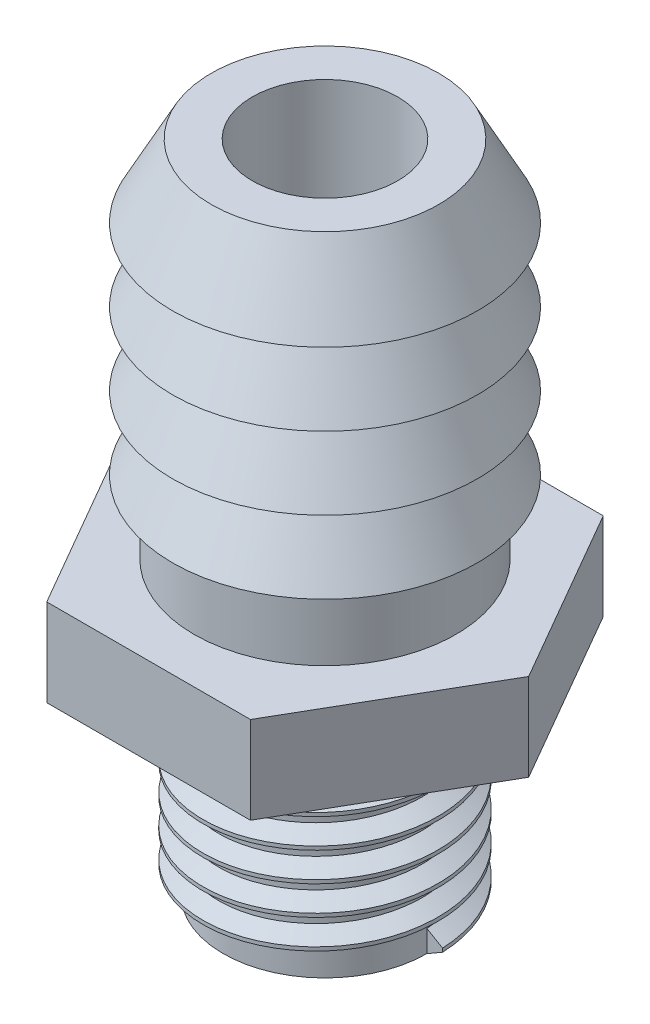
SolidWorks part; units mm, degrees
ref_plane "Front Plane" through (0, 0, 0) normal (0, 0, 1) x (1, 0, 0)
ref_plane "Top Plane" through (0, 0, 0) normal (0, 1, 0) x (1, 0, 0)
ref_plane "Right Plane" through (0, 0, 0) normal (1, 0, 0) x (0, 0, -1)
sketch "Sketch1" plane through (0, 0, 0) normal (0, 1, 0) x (1, 0, 0)
  circle A0 centre (0, 0) radius 5.2387
  dimension "D1" = 10.4775
extrude "Boss-Extrude1" add sketch "Sketch1" along normal blind 2.5 draft 28
sketch "Sketch2" plane through (0, 0, 0) normal (1, 0, 0) x (0, 0, -1)
  line L0 (0, 0) -> (0, 4.3347) construction
pattern_linear "LPattern1" count 4 spacing 2.5 along (0, -1, 0) of "Boss-Extrude1"
sketch "Sketch3" plane through (0, -7.5, 0) normal (0, -1, 0) x (1, 0, 0)
  circle A0 centre (0, 0) radius 2.5
  circle A1 centre (0, 0) radius 4.5
  point P4 (0, 0)
  dimension "D1" = 5
  dimension "D2" = 9
extrude "Boss-Extrude2" add sketch "Sketch3" along normal blind 2.5
sketch "Sketch5" plane through (0, -10, 0) normal (0, -1, 0) x (1, 0, 0)
  line L1 (3.5, 6.0622) -> (-3.5, 6.0622)
  line L2 (-3.5, 6.0622) -> (-7, 0)
  line L3 (-7, 0) -> (-3.5, -6.0622)
  line L4 (-3.5, -6.0622) -> (3.5, -6.0622)
  line L5 (3.5, -6.0622) -> (7, 0)
  line L6 (7, 0) -> (3.5, 6.0622)
  circle A0 centre (0, 0) radius 6.0622 construction
  point P1 (7, 0)
  point P10 (6.8268, -1.5473)
  dimension "D1" = 7
extrude "Boss-Extrude3" add sketch "Sketch5" along normal blind 3 contours L1 L2 L3 L4 L5 L6
sketch "Sketch4" plane through (0, -7.5, 0) normal (0, -1, 0) x (1, 0, 0)
  circle A1 centre (0, 0) radius 2.5
  circle A2 centre (0, 0) radius 2.5
  dimension "D1" = 0
extrude "Cut-Extrude1" cut sketch "Sketch4" against normal through all both and the other way through all
sketch "Sketch6" plane through (0, -13, 0) normal (0, -1, 0) x (1, 0, 0)
  circle A0 centre (0, 0) radius 3.5
  circle A1 centre (0, 0) radius 2.5 construction
  circle A2 centre (0, 0) radius 2.5
  dimension "D1" = 7
extrude "Boss-Extrude4" add sketch "Sketch6" along normal blind 7 separate body
thread "Thread2" pitch 1 start angle 0, offset 0, length 0, pitch 1, diameter 7
ref_plane "Plane3" through (3.5, -20, 0) normal (0, 0, 1) x (1, 0, 0)
sketch "Thread Profile3" plane through (3.5, -20, 0) normal (0, 0, 1) x (1, 0, 0)
  line L0 (0, 0) -> (0, 1) construction
  line L1 (0, 0) -> (0.5413, 0.3125)
  line L2 (0.5413, 0.3125) -> (0.5413, 0.4375)
  line L3 (0.5413, 0.4375) -> (0, 0.75)
  line L4 (0.5413, 0.375) -> (0, 0.375) construction
  line L11 (0, 0) -> (0, 0.75)
  point P2 (0, 0)
  dimension "Pitch" = 1
  dimension "Profile_Angle" = 60
  dimension "Profile_Land" = 0.125
  dimension "Profile_Height" = 0.5413
ref_plane "Plane4" through (4.0413, -19.5625, 0) normal (0, 0.0373, -0.9993) x (-1, 0, 0)
equation "\"TUBEID\"=7.9375"
equation "\"D1@Sketch1\"=\"TUBEID\"+2.54"
equation "\"H\"=2.5"
equation "\"D1@Boss-Extrude1\"=\"H\""
equation "\"ANGLE\"=28"
equation "\"D3@Boss-Extrude1\"=\"ANGLE\""
equation "\"D3@LPattern1\"=\"H\""
equation "\"ID\"=5"
equation "\"OD\"=9"
equation "\"L\"=2.5"
equation "\"NUT\"=7"
equation "\"D1@Sketch5\"=\"NUT\""
equation "\"NUTT\"=3"
equation "\"D1@Boss-Extrude2\"=\"L\""
equation "\"D2@Sketch3\"=\"OD\""
equation "\"D1@Sketch3\"=\"ID\""
equation "\"THREADL\"=3"
